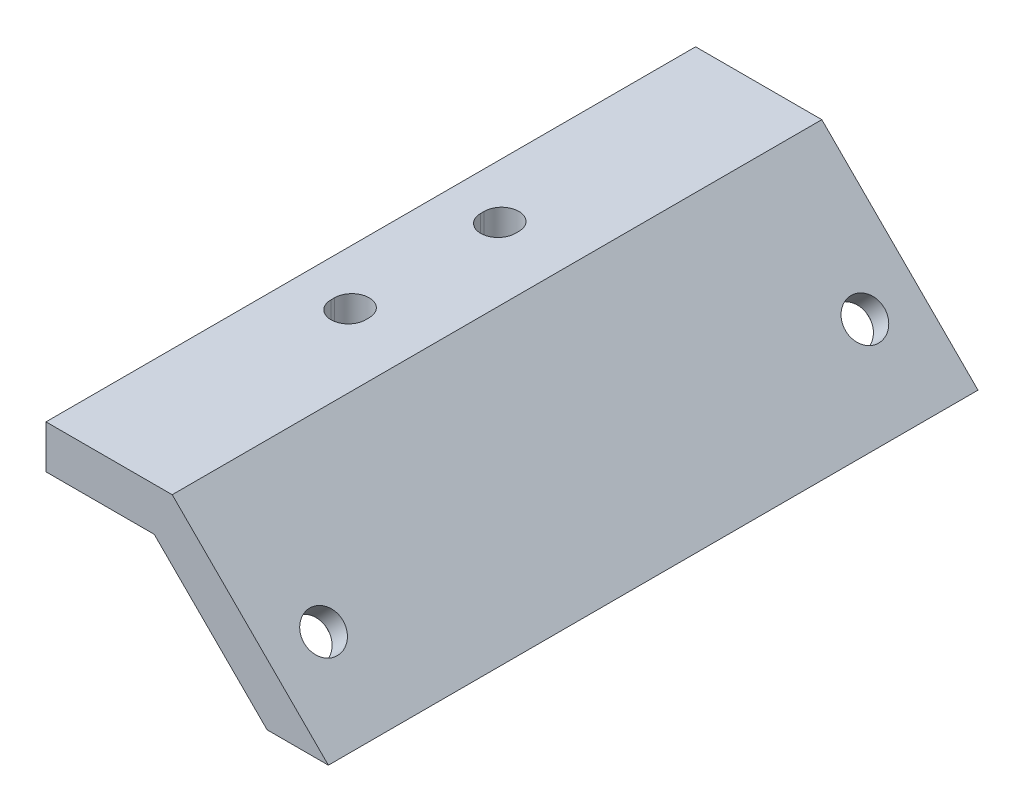
SolidWorks part; units mm, degrees
ref_plane "Alzado" through (0, 0, 0) normal (0, 0, 1) x (1, 0, 0)
ref_plane "Planta" through (0, 0, 0) normal (0, 1, 0) x (1, 0, 0)
ref_plane "Vista lateral" through (0, 0, 0) normal (1, 0, 0) x (0, 0, -1)
sketch "Croquis1" plane through (0, 0, 0) normal (0, 0, 1) x (1, 0, 0)
  line L0 (0, 0) -> (-14.425, 14.425)
  line L1 (-14.425, 14.425) -> (-26.0818, 14.425)
  line L2 (-26.0818, 14.425) -> (-26.0818, 10.425)
  line L3 (-26.0818, 10.425) -> (-16.0818, 10.425)
  line L4 (-16.0818, 10.425) -> (-5.6569, 0)
  line L5 (-5.6569, 0) -> (0, 0)
  line L6 (-14.425, 14.425) -> (-10.8894, 17.9605) construction
  line L7 (-10.8894, 17.9605) -> (7.0711, 0) construction
  line L8 (7.0711, 0) -> (0, 0) construction
  line L9 (-10.8894, 17.9605) -> (7.0711, 17.9605) construction
  line L10 (7.0711, 17.9605) -> (7.0711, 0) construction
  line L11 (-1.9092, 8.9803) -> (-8.2731, 2.6163) construction
  dimension "D1" = 25.4
  dimension "D2" = 5
  dimension "D3" = 4
  dimension "D4" = 4
  dimension "D5" = 10
  dimension "D6" = 11.0431
extrude "Saliente-Extruir1" add sketch "Croquis1" along normal blind 30 and the other way blind 30
ref_plane "Plano1" through (-2.8284, -2.8284, 0) normal (-0.7071, -0.7071, 0) x (-0.7071, 0.7071, 0)
sketch "Croquis2" plane through (-2.8284, -2.8284, 0) normal (-0.7071, -0.7071, 0) x (-0.7071, 0.7071, 0)
  line L0 (18.7431, 0) -> (7.7031, 0) construction
  line L1 (18.7431, 30) -> (18.7431, -30) construction
  line L2 (7.7031, 25) -> (7.7031, -25) construction
  circle A0 centre (7.7031, 25) radius 1.8
  circle A1 centre (7.7031, -25) radius 1.8
  circle A2 centre (7.7031, 25) radius 3.2
  circle A3 centre (7.7031, -25) radius 3.2
  point P7 (7.7031, 0)
  dimension "D3" = 3.6
  dimension "D4" = 6.4
  dimension "D1" = 11.04
  dimension "D2" = 50
extrude "Cortar-Extruir1" cut sketch "Croquis2" against normal up to surface (4 mm away) contours A1 | A0 region at (-8.2754, 2.6185, -25) region at (-8.2754, 2.6185, 25) up to face at (-7.2125, 7.2125, 0)
extrude "Cortar-Extruir2" cut sketch "Croquis2<3>" against normal blind 2
sketch "Croquis2<3>" plane through (-2.8284, -2.8284, 0) normal (-0.7071, -0.7071, 0) x (-0.7071, 0.7071, 0) same geometry as "Croquis2"
ref_plane "Plano2" through (0, 14.425, 0) normal (0, 1, 0) x (1, 0, 0)
sketch "Croquis3" plane through (0, 14.425, 0) normal (0, 1, 0) x (1, 0, 0)
  line L0 (-26.0818, 0) -> (-21.0818, 0) construction
  line L1 (-26.0818, 30) -> (-26.0818, -30) construction
  line L2 (-21.0818, 7.075) -> (-21.0818, -7.075) construction
  line L3 (-21.0818, 6.75) -> (-21.0818, -6.75)
  line L4 (-19.4818, 7.075) -> (-19.4818, 6.75)
  line L5 (-22.6818, 7.075) -> (-22.6818, 6.75)
  line L6 (-19.4818, -7.075) -> (-19.4818, -6.75)
  line L7 (-22.6818, -7.075) -> (-22.6818, -6.75)
  arc A0 (-19.4818, 7.075) -> (-22.6818, 7.075) centre (-21.0818, 7.075) ccw
  arc A1 (-22.6818, 6.75) -> (-19.4818, 6.75) centre (-21.0818, 6.75) ccw
  arc A2 (-19.4818, -6.75) -> (-22.6818, -6.75) centre (-21.0818, -6.75) ccw
  arc A3 (-22.6818, -7.075) -> (-19.4818, -7.075) centre (-21.0818, -7.075) ccw
  point P8 (-21.0818, 0)
  point P11 (-21.0818, 0)
  dimension "D4" = 3.2
  dimension "D1" = 5
  dimension "D2" = 14.15
  dimension "D3" = 13.5
extrude "Cortar-Extruir3" cut sketch "Croquis3" against normal up to surface (4 mm away) contours L5 A1 L4 A0 | L7 A3 L6 A2 region at (-21.0818, 14.425, 6.9125) region at (-21.0818, 14.425, -6.9125) up to face at (-21.0818, 10.425, 0)
